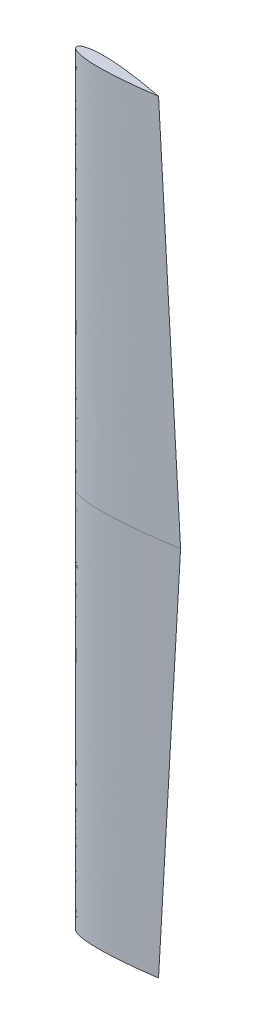
SolidWorks part; units mm, degrees
material "Polyurethane Foam Rigid"
ref_plane "Front Plane" through (0, 0, 0) normal (0, 0, 1) x (1, 0, 0)
ref_plane "Top Plane" through (0, 0, 0) normal (0, 1, 0) x (1, 0, 0)
ref_plane "Right Plane" through (0, 0, 0) normal (1, 0, 0) x (0, 0, -1)
sketch "rootSketch" plane through (0, 0, 0) normal (0, 1, 0) x (1, 0, 0)
  line L0 (0, 0) -> (1500, 0) construction
  line L2 (13.706, -4.2688) -> (13.7924, 3.9808) construction
  line L3 (0, 0) -> (54.997, -0.5759) construction
  spline S0 degree 4 poles (0, 0) (0, 0.0599) (0.0057, 0.1568) (0.0275, 0.2957) (0.0818, 0.4758) (0.1542, 0.6428) (0.2604, 0.8248) (0.4116, 1.0257) (0.6297, 1.2541) (0.9532, 1.522) (1.443, 1.8404) (2.1897, 2.2147) (3.3471, 2.6497) (5.0783, 3.1129) (7.6643, 3.5675) (11.005, 3.8809) (14.9069, 3.9995) (19.161, 3.9213) (22.8761, 3.7218) (26.0584, 3.4794) (29.2318, 3.1907) (31.8813, 2.9134) (34.512, 2.6093) (37.6912, 2.2074) (40.8239, 1.7838) (44.0298, 1.3101) (47.1078, 0.8251) (49.8344, 0.3648) (51.7333, 0.0349) (54.3896, -0.4558) (55.9036, -0.7484) (58.1126, -1.1904) (59.1885, -1.422) (60.0621, -1.6055) (60.2845, -1.6569) (60.5097, -1.7047) knots 0 0 0 0 0 0.003844 0.006241 0.009008 0.01207 0.015524 0.019766 0.025141 0.032337 0.04248 0.057257 0.078755 0.111734 0.157569 0.225948 0.294326 0.362704 0.431082 0.465271 0.49946 0.567838 0.602027 0.636216 0.704594 0.772972 0.807161 0.84135 0.875539 0.909728 0.954864 0.977432 0.988716 1 1 1 1 1 construction
  spline S1 degree 4 poles (0, 0) (0, 0.0599) (0.0057, 0.1568) (0.0275, 0.2957) (0.0818, 0.4758) (0.1542, 0.6428) (0.2604, 0.8248) (0.4116, 1.0257) (0.6297, 1.2541) (0.9532, 1.522) (1.443, 1.8404) (2.1897, 2.2147) (3.3471, 2.6497) (5.0783, 3.1129) (7.6643, 3.5675) (11.005, 3.8809) (14.9069, 3.9995) (19.161, 3.9213) (22.8761, 3.7218) (26.0584, 3.4794) (29.2318, 3.1907) (31.8813, 2.9134) (34.512, 2.6093) (37.6912, 2.2074) (40.8239, 1.7838) (44.0298, 1.3101) (47.1078, 0.8251) (49.8344, 0.3648) (51.7333, 0.0349) (53.5779, -0.3058) (54.5251, -0.4847) (55, -0.576) knots 0 0 0 0 0 0.003844 0.006241 0.009008 0.01207 0.015524 0.019766 0.025141 0.032337 0.04248 0.057257 0.078755 0.111734 0.157569 0.225948 0.294326 0.362704 0.431082 0.465271 0.49946 0.567838 0.602027 0.636216 0.704594 0.772972 0.807161 0.84135 0.875539 0.909728 0.909728 0.909728 0.909728 0.909728
  spline S2 degree 4 poles (0, 0) (-0.0013, -0.0599) (0.0024, -0.1569) (0.0213, -0.2962) (0.0718, -0.4774) (0.1407, -0.6459) (0.243, -0.8301) (0.39, -1.0341) (0.6033, -1.267) (0.9211, -1.5416) (1.4041, -1.8702) (2.1428, -2.2601) (3.2909, -2.7192) (5.012, -3.2185) (7.588, -3.7272) (10.9213, -4.1105) (14.8199, -4.3108) (19.0746, -4.3217) (22.7931, -4.2001) (25.9798, -4.0244) (29.1586, -3.8021) (31.8133, -3.5804) (34.4498, -3.3315) (37.6367, -2.9963) (40.7776, -2.6384) (43.9927, -2.2319) (47.0802, -1.8115) (49.8158, -1.4084) (51.7212, -1.1184) (54.3872, -0.6834) (55.907, -0.4225) (58.1248, -0.0269) (59.2053, 0.1821) (60.0826, 0.3473) (60.306, 0.394) (60.5321, 0.4371) knots 0 0 0 0 0 0.003844 0.006241 0.009008 0.01207 0.015524 0.019766 0.025141 0.032337 0.04248 0.057257 0.078755 0.111734 0.157569 0.225948 0.294326 0.362704 0.431082 0.465271 0.49946 0.567838 0.602027 0.636216 0.704594 0.772972 0.807161 0.84135 0.875539 0.909728 0.954864 0.977432 0.988716 1 1 1 1 1 construction
  spline S3 degree 4 poles (0, 0) (-0.0013, -0.0599) (0.0024, -0.1569) (0.0213, -0.2962) (0.0718, -0.4774) (0.1407, -0.6459) (0.243, -0.8301) (0.39, -1.0341) (0.6033, -1.267) (0.9211, -1.5416) (1.4041, -1.8702) (2.1428, -2.2601) (3.2909, -2.7192) (5.012, -3.2185) (7.588, -3.7272) (10.9213, -4.1105) (14.8199, -4.3108) (19.0746, -4.3217) (22.7931, -4.2001) (25.9798, -4.0244) (29.1586, -3.8021) (31.8133, -3.5804) (34.4498, -3.3315) (37.6367, -2.9963) (40.7776, -2.6384) (43.9927, -2.2319) (47.0802, -1.8115) (49.8158, -1.4084) (51.7212, -1.1184) (53.5725, -0.8163) (54.5233, -0.6573) (55, -0.576) knots 0 0 0 0 0 0.003844 0.006241 0.009008 0.01207 0.015524 0.019766 0.025141 0.032337 0.04248 0.057257 0.078755 0.111734 0.157569 0.225948 0.294326 0.362704 0.431082 0.465271 0.49946 0.567838 0.602027 0.636216 0.704594 0.772972 0.807161 0.84135 0.875539 0.909728 0.909728 0.909728 0.909728 0.909728
  point P10 (13.7492, -0.144)
  dimension "incidenceAngle" = 0.6
  dimension "rootChord" = 55
  dimension "rootQuarterChord" = 13.75
  dimension "rootMaxThickness" = 8.25
ref_plane "Plane1" through (0, 199.9998, 0) normal (0, 1, 0) x (1, 0, 0)
sketch "tipSketch" plane through (0, 199.9998, 0) normal (0, 1, 0) x (1, 0, 0)
  line L0 (218.7894, 0) -> (520.1012, 0) construction
  line L3 (0, 0) -> (43.9861, -1.1057) construction
  line L4 (10.9136, -3.5754) -> (11.0795, 3.0225) construction
  spline S0 degree 4 poles (0, 0) (0, 0.048) (0.0046, 0.1256) (0.0221, 0.237) (0.0658, 0.3807) (0.1242, 0.5139) (0.2093, 0.6583) (0.3299, 0.8163) (0.5028, 0.9947) (0.7572, 1.2022) (1.1448, 1.45) (1.7375, 1.7401) (2.6574, 2.0744) (4.0387, 2.4259) (6.1062, 2.7614) (8.7802, 2.9748) (11.9074, 3.0251) (15.3173, 2.9129) (18.7187, 2.6807) (21.6912, 2.3974) (24.2299, 2.1114) (26.7725, 1.7936) (28.875, 1.5087) (31.0006, 1.198) (33.0827, 0.8767) (34.8048, 0.5964) (36.8312, 0.2578) (39.0673, -0.1436) (40.9422, -0.4907) (43.5009, -1.0005) (44.7312, -1.2563) (46.4821, -1.6325) (47.357, -1.8333) (48.0453, -1.9882) (48.2302, -2.0334) (48.4072, -2.0736) knots 0 0 0 0 0 0.003846 0.006245 0.009023 0.012045 0.015501 0.01968 0.024954 0.031954 0.041824 0.056556 0.077861 0.110456 0.156157 0.224645 0.293132 0.36162 0.430108 0.498596 0.53284 0.567084 0.635571 0.669815 0.704059 0.738303 0.772547 0.841035 0.875279 0.909523 0.954761 0.977381 0.98869 1 1 1 1 1 construction
  spline S1 degree 4 poles (0, 0) (0, 0.048) (0.0046, 0.1256) (0.0221, 0.237) (0.0658, 0.3807) (0.1242, 0.5139) (0.2093, 0.6583) (0.3299, 0.8163) (0.5028, 0.9947) (0.7572, 1.2022) (1.1448, 1.45) (1.7375, 1.7401) (2.6574, 2.0744) (4.0387, 2.4259) (6.1062, 2.7614) (8.7802, 2.9748) (11.9074, 3.0251) (15.3173, 2.9129) (18.7187, 2.6807) (21.6912, 2.3974) (24.2299, 2.1114) (26.7725, 1.7936) (28.875, 1.5087) (31.0006, 1.198) (33.0827, 0.8767) (34.8048, 0.5964) (36.8312, 0.2578) (39.0673, -0.1436) (40.9422, -0.4907) (42.8656, -0.8739) (43.6203, -1.0276) (44, -1.1061) knots 0 0 0 0 0 0.003846 0.006245 0.009023 0.012045 0.015501 0.01968 0.024954 0.031954 0.041824 0.056556 0.077861 0.110456 0.156157 0.224645 0.293132 0.36162 0.430108 0.498596 0.53284 0.567084 0.635571 0.669815 0.704059 0.738303 0.772547 0.841035 0.875279 0.909523 0.909523 0.909523 0.909523 0.909523
  spline S2 degree 4 poles (0, 0) (-0.0024, -0.0479) (-0.0018, -0.1256) (0.0102, -0.2378) (0.0466, -0.3836) (0.0982, -0.5195) (0.176, -0.668) (0.2885, -0.8319) (0.4521, -1.0187) (0.6958, -1.2388) (1.0705, -1.5057) (1.6479, -1.8252) (2.5498, -2.2053) (3.9117, -2.6257) (5.9598, -3.0647) (8.6197, -3.4122) (11.7403, -3.6195) (15.1516, -3.6788) (18.5604, -3.6178) (21.5433, -3.4842) (24.0932, -3.3261) (26.6486, -3.1365) (28.7627, -2.9576) (30.9012, -2.7541) (32.9968, -2.5378) (34.7309, -2.3444) (36.7718, -2.1081) (39.0251, -1.8195) (40.9152, -1.567) (43.4962, -1.1864) (44.7378, -0.9927) (46.5054, -0.705) (47.3893, -0.5484) (48.0845, -0.4283) (48.2715, -0.3925) (48.4502, -0.3612) knots 0 0 0 0 0 0.003846 0.006245 0.009023 0.012045 0.015501 0.01968 0.024954 0.031954 0.041824 0.056556 0.077861 0.110456 0.156157 0.224645 0.293132 0.36162 0.430108 0.498596 0.53284 0.567084 0.635571 0.669815 0.704059 0.738303 0.772547 0.841035 0.875279 0.909523 0.954761 0.977381 0.98869 1 1 1 1 1 construction
  spline S3 degree 4 poles (0, 0) (-0.0024, -0.0479) (-0.0018, -0.1256) (0.0102, -0.2378) (0.0466, -0.3836) (0.0982, -0.5195) (0.176, -0.668) (0.2885, -0.8319) (0.4521, -1.0187) (0.6958, -1.2388) (1.0705, -1.5057) (1.6479, -1.8252) (2.5498, -2.2053) (3.9117, -2.6257) (5.9598, -3.0647) (8.6197, -3.4122) (11.7403, -3.6195) (15.1516, -3.6788) (18.5604, -3.6178) (21.5433, -3.4842) (24.0932, -3.3261) (26.6486, -3.1365) (28.7627, -2.9576) (30.9012, -2.7541) (32.9968, -2.5378) (34.7309, -2.3444) (36.7718, -2.1081) (39.0251, -1.8195) (40.9152, -1.567) (42.8554, -1.2809) (43.6169, -1.1654) (44, -1.1061) knots 0 0 0 0 0 0.003846 0.006245 0.009023 0.012045 0.015501 0.01968 0.024954 0.031954 0.041824 0.056556 0.077861 0.110456 0.156157 0.224645 0.293132 0.36162 0.430108 0.498596 0.53284 0.567084 0.635571 0.669815 0.704059 0.738303 0.772547 0.841035 0.875279 0.909523 0.909523 0.909523 0.909523 0.909523
  point P10 (10.9965, -0.2764)
  dimension "incidenceAngle" = 1.44
  dimension "tipChord" = 44
  dimension "tipQuarterChord" = 11
  dimension "tipMaxThickness" = 6.6
  dimension "sweepOffset" = 0
loft "Loft1" add profiles "rootSketch", "tipSketch" connector at (0, 0, 0) connector at (0, 199.9998, 0)
mirror "Mirror1" about plane through (0, 0, 0) normal (0, 1, 0) of "Loft1"
ref_plane "Plane2" through (55, 0, 0) normal (1, 0, 0) x (0, 0, -1)
sketch "elevatorSketch" plane through (0, 0, 0) normal (0, 0, 1) x (1, 0, 0)
  line L0 (33.3998, 0.0132) -> (28.4634, 149.5999)
  line L1 (0, 149.9998) -> (28.05, 149.9998) construction
  line L2 (0, 0) -> (33, 0) construction
  line L3 (-0.0003, 0) -> (55, 0) construction
  line L4 (33, 0) -> (28.05, 149.9998)
  line L5 (28.4634, 149.5999) -> (83.05, 149.5999)
  line L7 (28.05, 149.9998) -> (83.05, 149.9998)
  line L8 (33, 0) -> (33.3998, 0.0132)
  line L9 (83.05, 149.9998) -> (83.05, 149.5999)
  dimension "elevatorEndyLoc" = 149.9998
  dimension "elevatorEndxLoc" = 28.05
  dimension "D1" = 33
  dimension "D2" = 55
  dimension "D3" = 0.4
extrude "Cut-Extrude2" [suppressed] cut sketch "elevatorSketch" against normal blind 200 and the other way blind 200 contours L0 L5 L9 L7 L4 L8
mirror "Mirror2" [suppressed] about plane through (0, 0, 0) normal (0, 1, 0)
equation "\"rootChord@rootSketch\"=(\"rootChord\"+\"rootChord\")/2"
equation "\"rootQuarterChord@rootSketch\" = \"rootChord@rootSketch\" / 4"
equation "\"rootMaxThickness@rootSketch\" = \"rootChord\" * \"NACAairfoil\" / 100"
equation "\"halfSpan@Plane1\"=\"halfSpan\""
equation "\"tipQuarterChord@tipSketch\"=\"tipChord@tipSketch\"/4"
equation "\"tipMaxThickness@tipSketch\"=\"tipChord@tipSketch\"*\"NACAairfoil\"/100"
equation "\"rootChord@Plane2\"=\"rootChord@rootSketch\""
equation "\"elevatorWidth\"= 0.75'Elevator width as a percentage of H-stab span"
equation "\"elevatorEndyLoc@elevatorSketch\"=\"elevatorWidth\"*\"halfSpan@Plane1\""
equation "\"elevatorEndxLoc@elevatorSketch\"=\"elevatorEndyLoc@elevatorSketch\" * tan ( \"sweepAngle\" )  + 0.6 *  ( \"rootChord@rootSketch\" + \"elevatorEndyLoc@elevatorSketch\" *  (  (  ( \"tipChord@tipSketch\" - \"rootChord@rootSketch\" )  / \"halfSpan@Plane1\" )  )  )"
equation "\"D1@elevatorSketch\"=0.6*\"rootChord@rootSketch\""
equation "\"D2@elevatorSketch\"=1*\"rootChord@rootSketch\""
equation "\"D3@elevatorSketch\" = \"halfSpan\" / 500"
equation "\"halfSpan\"= \"rootChord\" * ( 1 + \"taperRatio\" ) / 2 * \"aspectRatio\" / 2'H-stab half Span"
equation "\"sweepOffset@tipSketch\" = \"halfSpan\" * tan ( \"sweepAngle\" ) "
equation "\"incidenceAngle@rootSketch\"=\"incidentAngle\""
equation "\"rootChord\"= 0.055"
equation "\"NACAairfoil\"= 0015"
equation "\"incidentAngle\"= -0.25"
equation "\"aspectRatio\"= 8.0808"
equation "\"taperRatio\"= 0.8"
equation "\"sweepAngle\"= 0"
equation "\"tipChord@tipSketch\"=\"rootChord\"*\"taperRatio\""
